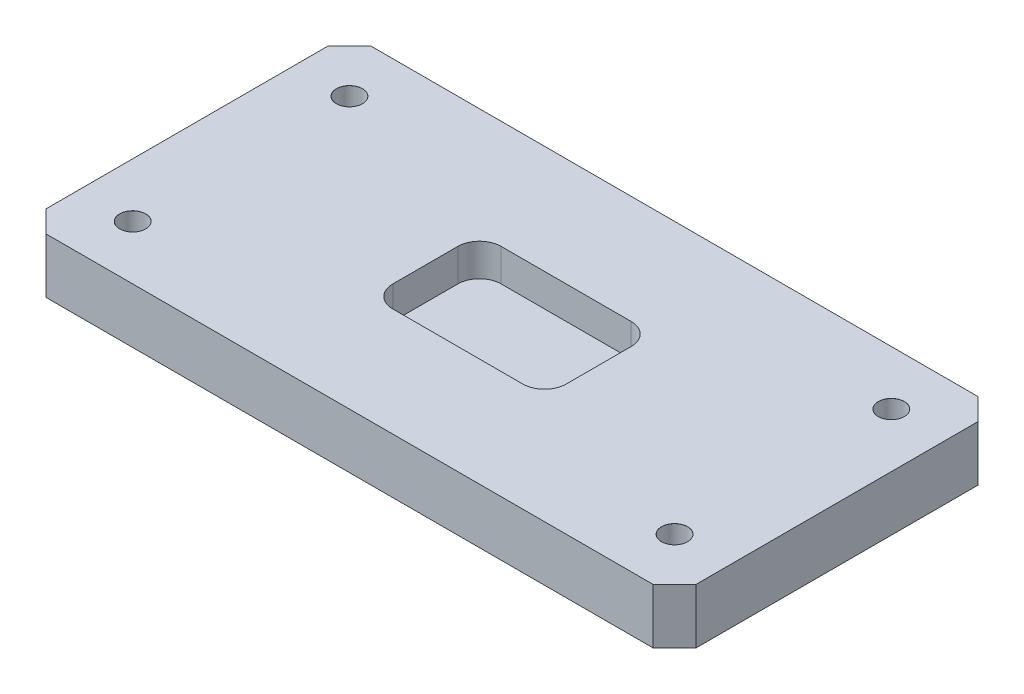
SolidWorks part; units mm, degrees
note: '?' marks a value the reader was unsure of.
ref_plane "Front Plane" through (0, 0, 0) normal (0, 0, 1) x (1, 0, 0)
ref_plane "Top Plane" through (0, 0, 0) normal (0, 1, 0) x (1, 0, 0)
ref_plane "Right Plane" through (0, 0, 0) normal (1, 0, 0) x (0, 0, -1)
ref_axis "X AXIS" through (-88.99, 0, 0) along (1, 0, 0)?
ref_axis "Y AXIS" through (0, 55, 0) along (0, -1, 0)?
ref_axis "Z AXIS" through (0, 0, -88.99) along (0, 0, 1)?
sketch "Sketch1" plane through (0, 0, 0) normal (0, 1, 0) x (1, 0, 0)
  line L0 (-150, 65) -> (-140, 75)
  line L1 (-140, 75) -> (140, 75)
  line L2 (-150, 65) -> (-150, -65)
  line L3 (-140, -75) -> (140, -75)
  line L4 (150, 65) -> (150, -65)
  line L5 (-150, 75) -> (150, -75) construction
  line L6 (-150, -75) -> (150, 75) construction
  line L7 (-150, -65) -> (-140, -75)
  line L8 (140, -75) -> (150, -65)
  line L9 (140, 75) -> (150, 65)
  point P0 (0, 0)
  point P14 (-150, 75)
  point P17 (-150, -75)
  point P18 (150, -75)
  point P19 (150, 75)
  dimension "D1" = 300
  dimension "D2" = 150
extrude "Boss-Extrude1" add sketch "Sketch1" along normal blind 25.4
hole_wizard "CBORE for M10 Hex Head Bolt1" [suppressed] positions "Sketch2" profile "Sketch3" counterbore size "M10" standard "ANSI Metric"
sketch "Sketch2" plane through (0, 25.4, 0) normal (0, 1, 0) x (1, 0, 0)
  line L0 (0, 0) -> (0, 95.6355) construction
  line L2 (0, 0) -> (107.4622, 0) construction
  line L5 (-150, 65) -> (-150, -65) construction
  line L6 (140, 75) -> (-140, 75) construction
  point P0 (-125, 50)
  point P20 (125, 50)
  point P21 (125, -50)
  point P22 (-125, -50)
  dimension "D1" = 25
  dimension "D2" = 25
sketch "Sketch3" plane through (-125, 25.4, -50) normal (1, 0, 0) x (0, 0, 1)
  line L0 (0, 0) -> (0, 25.4)
  line L1 (0, 25.4) -> (5.5, 25.4)
  line L3 (5.5, 25.4) -> (5.5, 6.85)
  line L4 (10.74, 6.85) -> (5.5, 6.85)
  line L5 (10.74, 6.85) -> (10.74, 0.021)
  line L6 (10.74, 0.021) -> (10.765, 0)
  line L7 (10.765, 0) -> (0, 0)
  line L8 (-10.74, 0.021) -> (-10.765, 0) construction
  line L11 (0, -6.35) -> (0, 107.95) construction
  dimension "Thru Hole Dia." = 11
  dimension "Thru Hole Depth" = 25.4
  dimension "C'Bore Dia." = 21.48
  dimension "C'Bore Depth" = 6.85
  dimension "Near C'Sink Dia." = 21.53
  dimension "Near C'Sink Angle" = 100
sketch "Sketch4" plane through (0, 25.4, 0) normal (0, 1, 0) x (1, 0, 0)
  line L1 (-40, 25) -> (40, 25)
  line L2 (-40, 25) -> (-40, -25)
  line L3 (-40, -25) -> (40, -25)
  line L4 (40, 25) -> (40, -25)
  line L5 (-40, 25) -> (40, -25) construction
  line L6 (-40, -25) -> (40, 25) construction
  point P0 (0, 0)
  dimension "D1" = 80
  dimension "D2" = 50
extrude "Cut-Extrude1" cut sketch "Sketch4" against normal blind 15
fillet "Fillet1" radius 10 4 edges at (-40, 17.9, 25) (40, 17.9, 25) (-40, 17.9, -25) (40, 17.9, -25)
hole_wizard "Ø12.0mm Dowel Hole1" positions "Sketch5" profile "Sketch6" hole size "Ø12.0" standard "ANSI Metric" end condition through all
sketch "Sketch5" plane through (0, 25.4, 0) normal (0, 1, 0) x (1, 0, 0)
  line L0 (-150, 65) -> (-150, -65) construction
  line L1 (140, 75) -> (-140, 75) construction
  line L2 (0, 0) -> (0, 75) construction
  line L4 (0, 0) -> (150, 0) construction
  line L5 (150, -65) -> (150, 65) construction
  point P0 (-125, 50)
  point P19 (125, 50)
  point P20 (125, -50)
  point P21 (-125, -50)
  dimension "D1" = 25
  dimension "D2" = 25
sketch "Sketch6" plane through (-125, 25.4, -50) normal (1, 0, 0) x (0, 0, 1)
  line L0 (0, 0) -> (0, 25.4)
  line L1 (0, 25.4) -> (6, 25.4)
  line L2 (6, 25.4) -> (6, 0.021)
  line L3 (6, 0.021) -> (6.025, 0)
  line L5 (6.025, 0) -> (0, 0)
  line L6 (-6, 0.021) -> (-6.025, 0) construction
  line L11 (0, -6.35) -> (0, 107.95) construction
  dimension "Thru Hole Dia." = 12
  dimension "Thru Hole Depth" = 25.4
  dimension "Near C'Sink Dia." = 12.05
  dimension "Near C'Sink Angle" = 100
